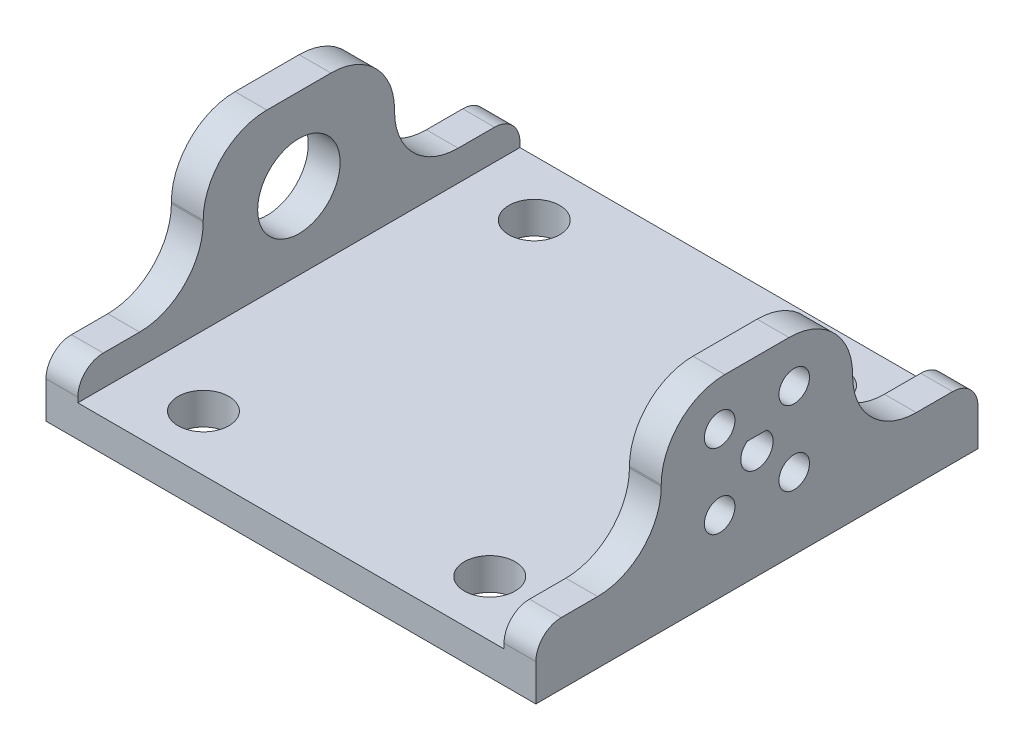
SolidWorks part; units mm, degrees
ref_plane "Front Plane" through (0, 0, 0) normal (0, 0, 1) x (1, 0, 0)
ref_plane "Top Plane" through (0, 0, 0) normal (0, 1, 0) x (1, 0, 0)
ref_plane "Right Plane" through (0, 0, 0) normal (1, 0, 0) x (0, 0, -1)
sketch "Sketch1" plane through (0, 0, 0) normal (0, 1, 0) x (1, 0, 0)
  line L1 (-38.5, 34.75) -> (38.5, 34.75)
  line L2 (-38.5, 34.75) -> (-38.5, -34.75)
  line L3 (-38.5, -34.75) -> (38.5, -34.75)
  line L4 (38.5, 34.75) -> (38.5, -34.75)
  line L5 (-38.5, 34.75) -> (38.5, -34.75) construction
  line L6 (-38.5, -34.75) -> (38.5, 34.75) construction
  line L7 (-38.5, 34.75) -> (-33.5, 34.75)
  line L8 (-38.5, 34.75) -> (-38.5, -34.75)
  line L9 (-38.5, -34.75) -> (-33.5, -34.75)
  line L10 (-33.5, 34.75) -> (-33.5, -34.75)
  line L11 (38.5, 34.75) -> (33.5, 34.75)
  line L12 (38.5, 34.75) -> (38.5, -34.75)
  line L13 (38.5, -34.75) -> (33.5, -34.75)
  line L14 (33.5, 34.75) -> (33.5, -34.75)
  point P0 (0, 0)
  dimension "D1" = 77
  dimension "D2" = 69.5
  dimension "D3" = 5
  dimension "D4" = 5
extrude "Boss-Extrude1" add sketch "Sketch1" along normal blind 30 contours L10 L1 L2 L3 | L1 L14 L3 L4 region at (-36, 0, 0) region at (36, 0, 0)
extrude "Boss-Extrude3" add sketch "Sketch1<4>" along normal blind 5 contours L14 L1 L10 L3 region at (0, 0, 0)
sketch "Sketch1<4>" plane through (0, 0, 0) normal (0, 1, 0) x (1, 0, 0) same geometry as "Sketch1"
sketch "Sketch2" plane through (-38.5, 0, 0) normal (-1, 0, 0) x (0, 0, 1)
  circle A1 centre (0, 17.1246) radius 6.477
  dimension "D2" = 12.954
extrude "Cut-Extrude1" cut sketch "Sketch2" against normal blind 34
sketch "Sketch3" plane through (0, 5, 0) normal (0, 1, 0) x (1, 0, 0)
  line L0 (0, 34.75) -> (0, -34.75) construction
  line L1 (-33.5, 34.75) -> (33.5, 34.75) construction
  line L2 (-33.5, -34.75) -> (33.5, -34.75) construction
  line L3 (-33.5, 0) -> (33.5, 0) construction
  line L4 (33.5, 34.75) -> (33.5, -34.75) construction
  circle A0 centre (-22.5, 26) radius 4
  circle A1 centre (-22.5, -26) radius 4
  circle A2 centre (22.5, 26) radius 4
  circle A3 centre (22.5, -26) radius 4
  point P12 (0, 0)
  dimension "D1" = 8
  dimension "D2" = 22.5
  dimension "D3" = 52
extrude "Cut-Extrude2" cut sketch "Sketch3" against normal blind 119
sketch "Sketch8" plane through (38.5, 0, 0) normal (1, 0, 0) x (0, 0, -1)
  line L0 (-6.477, 17.1246) -> (6.477, 17.1246) construction
  line L1 (0, 23.6016) -> (0, 10.6476) construction
  line L2 (-1.524, 19.1566) -> (1.524, 19.1566)
  circle A0 centre (0, 17.1246) radius 6.477 construction
  arc A1 (-1.524, 19.1566) -> (1.524, 19.1566) centre (0, 17.1246) ccw
  point P8 (0, 17.1246)
  point P13 (0, 19.1566)
  dimension "D1" = 5.08
  dimension "D2" = 2.032
extrude "Cut-Extrude3" cut sketch "Sketch8" against normal blind 14
sketch "Sketch9" plane through (-38.5, 0, 0) normal (-1, 0, 0) x (0, 0, 1)
  line L0 (-15.0399, 30) -> (-15.0399, 9.7741)
  line L1 (-34.75, 30) -> (34.75, 30) construction
  line L2 (-15.0399, 9.7741) -> (-34.75, 9.7741)
  line L3 (-34.75, 30) -> (-34.75, 0) construction
  line L4 (0, 30) -> (0, 0) construction
  line L5 (15.0399, 9.7741) -> (34.75, 9.7741)
  line L6 (15.0399, 30) -> (15.0399, 9.7741)
  line L7 (-34.75, 30) -> (-34.75, 9.7741)
  line L8 (-34.75, 30) -> (-15.0399, 30)
  line L9 (34.75, 30) -> (15.0399, 30)
  line L10 (34.75, 30) -> (34.75, 9.7741)
extrude "Cut-Extrude4" cut sketch "Sketch9" against normal blind 113
fillet "Fillet1" radius 10 8 edges at (36, 9.7741, -15.0399) (36, 9.7741, 15.0399) (36, 30, 15.0399) (36, 30, -15.0399) (-36, 30, -15.0399) (-36, 30, 15.0399) (-36, 9.7741, 15.0399) (-36, 9.7741, -15.0399)
fillet "Fillet2" radius 4 4 edges at (36, 9.7741, 34.75) (-36, 9.7741, 34.75) (-36, 9.7741, -34.75) (36, 9.7741, -34.75)
sketch "Sketch11" plane through (33.5, 0, 0) normal (-1, 0, 0) x (0, 0, 1)
  circle A0 centre (-5.8563, 22.9809) radius 2.4003
  circle A1 centre (5.8563, 22.9809) radius 2.4003
  circle A2 centre (-5.8563, 11.2683) radius 2.4003
  circle A3 centre (5.8563, 11.2683) radius 2.4003
  dimension "D1" = 4.8006
  dimension "D2" = 4.8006
  dimension "D3" = 4.8006
  dimension "D4" = 4.8006
extrude "Cut-Extrude5" cut sketch "Sketch11" against normal up to surface (5 mm away) up to face at (38.5, 13.7035, 0)
